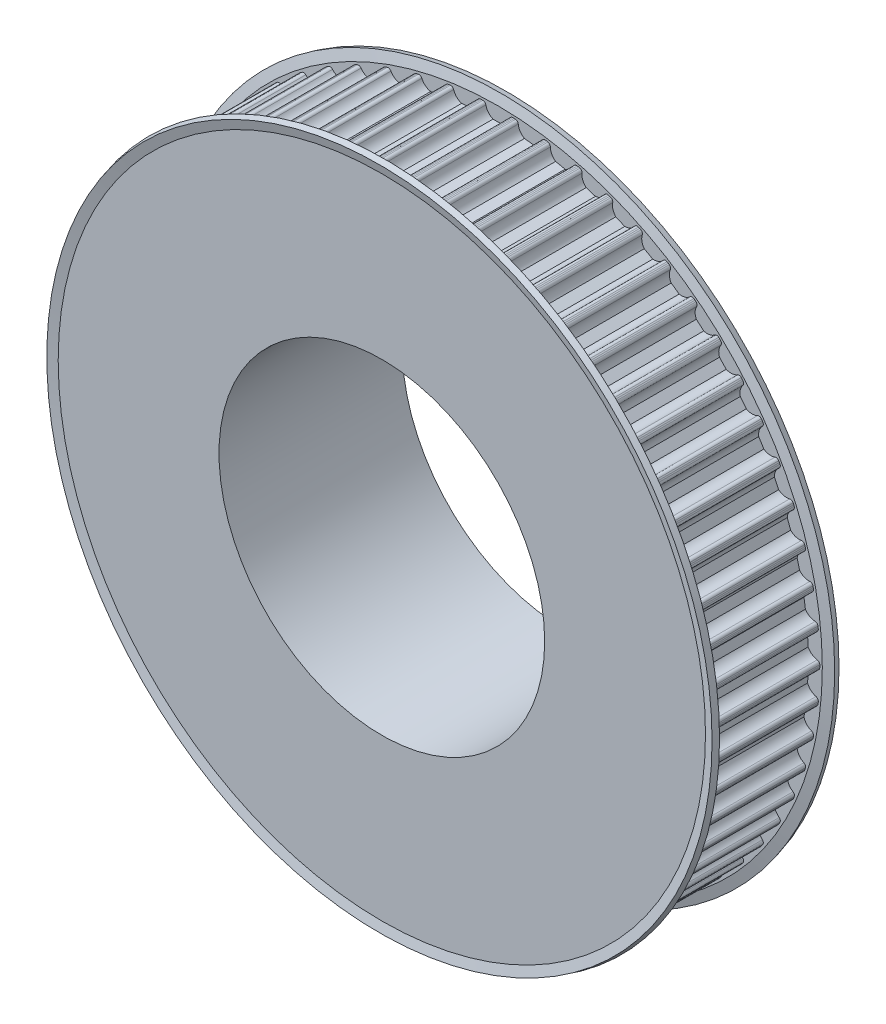
SolidWorks part; units mm, degrees
ref_plane "Front Plane" through (0, 0, 0) normal (0, 0, 1) x (1, 0, 0)
ref_plane "Top Plane" through (0, 0, 0) normal (0, 1, 0) x (1, 0, 0)
ref_plane "Right Plane" through (0, 0, 0) normal (1, 0, 0) x (0, 0, -1)
ref_axis "Axis1" through (0, 0, 55) along (0, 0, -1)
sketch "Sketch1" plane through (0, 0, 0) normal (1, 0, 0) x (0, 0, -1)
  line L0 (0, 40) -> (0, 80)
  line L1 (0, 80) -> (30, 80)
  line L2 (30, 80) -> (30, 55.5)
  line L3 (30, 55.5) -> (45, 55.5)
  line L4 (45, 55.5) -> (45, 40)
  line L5 (45, 40) -> (0, 40)
  dimension "D1" = 40
  dimension "D2" = 30
  dimension "D3" = 15
  dimension "D4" = 15.5
  dimension "D5" = 40
revolve "Revolve1" add sketch "Sketch1" angle 360 about axis through (0, 0, 55) along (0, 0, -1)
sketch "Sketch2" plane through (0, 0, 0) normal (0, 0, 1) x (1, 0, 0)
  line L0 (3.6742, 79) -> (4.25, 79)
  line L1 (-4, 81) -> (4.25, 81)
  line L2 (-4, 81) -> (-4, 79)
  line L3 (-4, 79) -> (-3.6742, 79)
  line L4 (4.25, 81) -> (4.25, 79)
  line L5 (-1.199, 76.25) -> (1.199, 76.25)
  arc A0 (-2.9394, 78.4) -> (-1.199, 76.25) centre (0, 79) ccw
  arc A1 (-2.9394, 78.4) -> (-3.6742, 79) centre (-3.6742, 78.25) ccw
  arc A2 (2.9394, 78.4) -> (3.6742, 79) centre (3.6742, 78.25) cw
  arc A3 (1.199, 76.25) -> (2.9394, 78.4) centre (0, 79) ccw
  point P11 (-3, 79)
  point P14 (3, 79)
  dimension "D1" = 3
  dimension "D5" = 0.75
  dimension "D6" = 0.75
  dimension "D2" = 2
  dimension "D3" = 8.25
  dimension "D4" = 79
  dimension "D7" = 2.75
extrude "Cut-Extrude1" cut sketch "Sketch2" against normal through all
pattern_circular "CirPattern1" count 62 over 360 about axis through (0, 0, 55) along (0, 0, -1) of "Cut-Extrude1"
sketch "Sketch3" plane through (0, 0, 0) normal (1, 0, 0) x (0, 0, -1)
  line L0 (0, 78.2951) -> (0, 75.9801) construction
  line L1 (0, 74.7) -> (1.5, 74.7)
  line L2 (0, 74.7) -> (0, 79.7)
  line L3 (0, 79.7) -> (1.5, 79.7) construction
  line L4 (1.5, 74.7) -> (1.5, 79.7)
  line L5 (1.5, 79.7) -> (0.0511, 79.3118) construction
  line L6 (1.5, 79.7) -> (0.8569, 82.1)
  line L7 (0.0511, 79.3118) -> (-0.592, 81.7118)
  line L8 (0.8569, 82.1) -> (-0.592, 81.7118)
  line L9 (0, 79) -> (30, 79) construction
  line L10 (15, 78.9664) -> (15, -33.0182) construction
  line L11 (30, 78.9664) -> (0, 78.9664) construction
  line L12 (28.5, 79.7) -> (29.9489, 79.3118) construction
  line L13 (30, 79.7) -> (28.5, 79.7) construction
  line L14 (29.1431, 82.1) -> (30.592, 81.7118)
  line L15 (29.9489, 79.3118) -> (30.592, 81.7118)
  line L16 (28.5, 79.7) -> (29.1431, 82.1)
  line L17 (28.5, 74.7) -> (28.5, 79.7)
  line L18 (30, 74.7) -> (30, 79.7)
  line L19 (30, 74.7) -> (28.5, 74.7)
  dimension "D1" = 1.5
  dimension "D2" = 5
  dimension "D3" = 1.5
  dimension "D4" = 2.4
  dimension "D5" = 165
  dimension "D6" = 0.7
revolve "Revolve2" add sketch "Sketch3" angle 360 about axis through (0, 0, 55) along (0, 0, -1) region at (0, 78.3312, -0.6556) region at (0, 78.3312, -29.3444)
